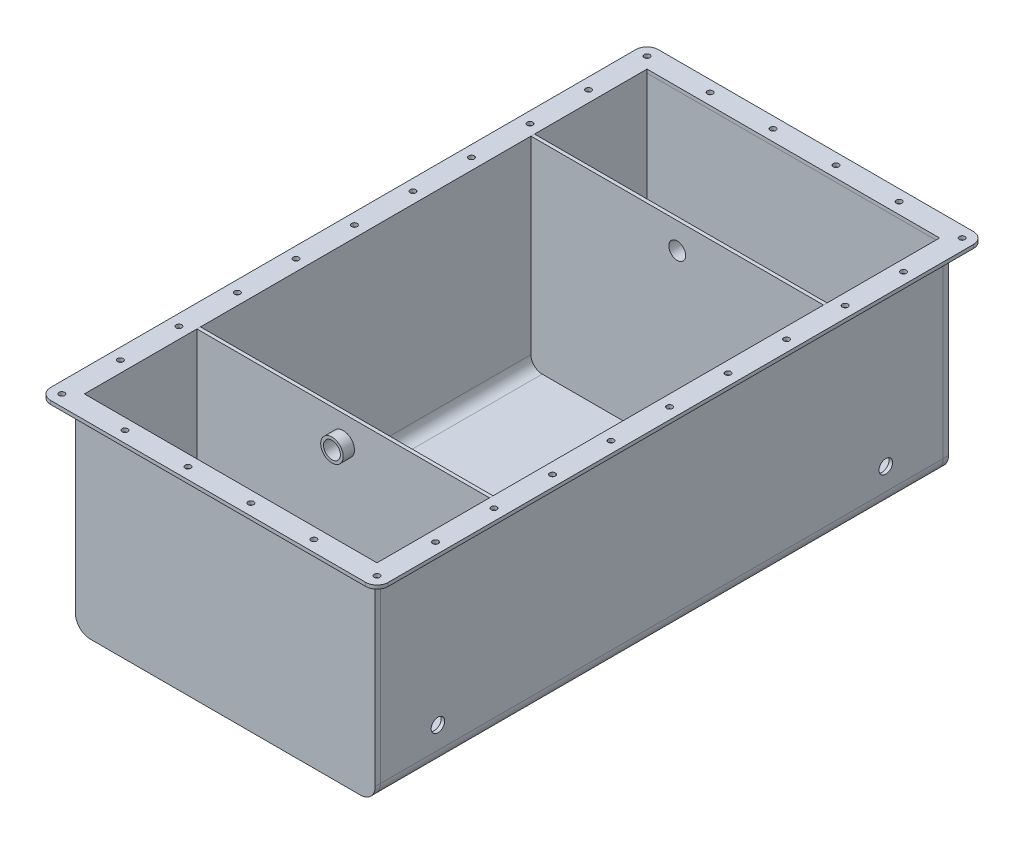
SolidWorks part; units mm, degrees
material "5052-H32"
ref_plane "Front Plane" through (0, 0, 0) normal (0, 0, 1) x (1, 0, 0)
ref_plane "Top Plane" through (0, 0, 0) normal (0, 1, 0) x (1, 0, 0)
ref_plane "Right Plane" through (0, 0, 0) normal (1, 0, 0) x (0, 0, -1)
sketch "Sketch2" plane through (0, 0, 0) normal (0, 0, 1) x (1, 0, 0)
  line L0 (-130, 0) -> (130, 0)
  line L1 (-130, 0) -> (-130, 175)
  line L2 (130, 0) -> (130, 175)
  line L3 (-133.175, -3.175) -> (-133.175, 175)
  line L4 (-133.175, -3.175) -> (133.175, -3.175)
  line L5 (133.175, -3.175) -> (133.175, 175)
  line L6 (-133.175, 175) -> (-130, 175)
  line L7 (130, 175) -> (133.175, 175)
  point P4 (0, 0)
  dimension "D1" = 260
  dimension "D3" = 175
  dimension "D4" = 175
  dimension "D2" = 3.175
  dimension "D5" = 3.175
  dimension "D6" = 3.175
extrude "Interior Dim" add sketch "Sketch2" against normal blind 500
fillet "Fillet2" radius 10 2 edges at (-130, 0, -250) (130, 0, -250)
fillet "Fillet3" radius 13.175 2 edges at (-133.175, -3.175, -250) (133.175, -3.175, -250)
ref_plane "Plane1" through (0, 0, 0) normal (0, 0, 1) x (1, 0, 0)
sketch "Sketch4" plane through (0, 0, 0) normal (0, 0, 1) x (1, 0, 0)
  line L0 (-130, 175) -> (130, 175)
  line L9 (-120, -3.175) -> (120, -3.175)
  line L10 (133.175, 10) -> (133.175, 175)
  line L11 (133.175, 175) -> (130, 175)
  line L12 (130, 175) -> (130, 10)
  line L13 (120, 0) -> (-120, 0)
  line L14 (-130, 10) -> (-130, 175)
  line L15 (-130, 175) -> (-133.175, 175)
  line L16 (-133.175, 175) -> (-133.175, 10)
  line L17 (-120, -3.175) -> (120, -3.175)
  line L18 (133.175, 10) -> (133.175, 175)
  line L19 (133.175, 175) -> (130, 175)
  line L23 (-130, 175) -> (-133.175, 175)
  line L24 (-133.175, 175) -> (-133.175, 10)
  arc A4 (120, -3.175) -> (133.175, 10) centre (120, 10) ccw
  arc A5 (120, 0) -> (130, 10) centre (120, 10) ccw
  arc A6 (-130, 10) -> (-120, 0) centre (-120, 10) ccw
  arc A7 (120, -3.175) -> (133.175, 10) centre (120, 10) ccw
  arc A9 (-133.175, 10) -> (-120, -3.175) centre (-120, 10) ccw
  arc A10 (-133.175, 10) -> (-120, -3.175) centre (-120, 10) ccw
  dimension "D1" = 0
extrude "Endcap1" add sketch "Sketch4" along normal blind 4.7625 separate body
ref_plane "Plane2" through (0, 0, -500) normal (0, 0, -1) x (-1, 0, 0)
sketch "Sketch5" plane through (0, 0, -500) normal (0, 0, -1) x (-1, 0, 0)
  line L8 (133.175, 175) -> (-133.175, 175)
  line L16 (-133.175, 175) -> (-133.175, 10)
  line L17 (-120, -3.175) -> (120, -3.175)
  line L18 (133.175, 10) -> (133.175, 175)
  line L19 (133.175, 175) -> (130, 175)
  line L20 (130, 175) -> (130, 10)
  line L21 (120, 0) -> (-120, 0)
  line L22 (-130, 10) -> (-130, 175)
  line L23 (-130, 175) -> (-133.175, 175)
  line L24 (-133.175, 175) -> (-133.175, 10)
  line L25 (-120, -3.175) -> (120, -3.175)
  line L26 (133.175, 10) -> (133.175, 175)
  arc A6 (-133.175, 10) -> (-120, -3.175) centre (-120, 10) ccw
  arc A7 (-133.175, 10) -> (-120, -3.175) centre (-120, 10) ccw
  arc A8 (120, 0) -> (130, 10) centre (120, 10) ccw
  arc A9 (-130, 10) -> (-120, 0) centre (-120, 10) ccw
  arc A12 (120, -3.175) -> (133.175, 10) centre (120, 10) ccw
  arc A13 (120, -3.175) -> (133.175, 10) centre (120, 10) ccw
  dimension "D1" = 0
ref_plane "Compartment1" through (0, 0, -100) normal (0, 0, -1) x (-1, 0, 0)
sketch "Sketch7" plane through (0, 0, -100) normal (0, 0, -1) x (-1, 0, 0)
  line L1 (130, 175) -> (-130, 175)
  line L10 (-120, -3.175) -> (120, -3.175)
  line L11 (-133.175, 175) -> (-133.175, 10)
  line L12 (-130, 175) -> (-133.175, 175)
  line L13 (-130, 10) -> (-130, 175)
  line L14 (120, 0) -> (-120, 0)
  line L15 (130, 175) -> (130, 10)
  line L16 (133.175, 175) -> (130, 175)
  line L17 (133.175, 10) -> (133.175, 175)
  line L21 (-130, 10) -> (-130, 175)
  line L22 (120, 0) -> (-120, 0)
  line L23 (130, 175) -> (130, 10)
  arc A5 (-130, 10) -> (-120, 0) centre (-120, 10) ccw
  arc A6 (120, 0) -> (130, 10) centre (120, 10) ccw
  arc A7 (-133.175, 10) -> (-120, -3.175) centre (-120, 10) ccw
  arc A8 (120, -3.175) -> (133.175, 10) centre (120, 10) ccw
  arc A9 (-130, 10) -> (-120, 0) centre (-120, 10) ccw
  arc A10 (120, 0) -> (130, 10) centre (120, 10) ccw
  dimension "D1" = 0
extrude "Compartment1_Boss" add sketch "Sketch7" along normal blind 3.175 separate body contours L22 A10 L23 L1 L21 A9 region at (0, 87.5805, -100)
ref_plane "Plane5" through (0, 175, 0) normal (0, 1, 0) x (1, 0, 0)
sketch "Sketch9" plane through (0, 175, 0) normal (0, 1, 0) x (1, 0, 0)
  line L0 (97.9962, 500) -> (-97.9962, 500) construction
  line L1 (-130, 500) -> (130, 500)
  line L2 (-130, 500) -> (-130, 0)
  line L3 (-130, 0) -> (130, 0)
  line L4 (130, 500) -> (130, 0)
  line L5 (-130, 0) -> (-130, 500) construction
  line L6 (-97.9962, 0) -> (97.9962, 0) construction
  line L7 (130, 500) -> (130, 0) construction
  line L8 (-150, 520) -> (-150, -20)
  line L9 (-150, -20) -> (150, -20)
  line L10 (150, 520) -> (150, -20)
  line L11 (-150, 520) -> (150, 520)
extrude "Lid_Flange" add sketch "Sketch9" along normal blind 3.175 separate body contours L11 L8 L9 L10 L1 L4 region at (0, 175, -513.8226)
fillet "Fillet4" radius 10 4 edges at (-150, 176.5875, -520) (150, 176.5875, -520) (150, 176.5875, 20) (-150, 176.5875, 20)
extrude "Endcap2" add sketch "Sketch5" along normal blind 4.7625 separate body
ref_plane "Compartment2" through (0, 0, -400) normal (0, 0, 1) x (1, 0, 0)
sketch "Sketch13" plane through (0, 0, -400) normal (0, 0, 1) x (1, 0, 0)
  line L0 (130, 175) -> (-130, 175)
  line L1 (133.175, 175) -> (130, 175) construction
  line L2 (130, 175) -> (130, 10) construction
  line L3 (-140, 175) -> (140, 175) construction
  line L4 (-130, 10) -> (-130, 175) construction
  line L5 (130, 175) -> (130, 10)
  line L6 (-130, 175) -> (-130, 10)
  line L7 (120, 0) -> (-120, 0)
  arc A0 (120, 0) -> (130, 10) centre (120, 10) ccw construction
  arc A1 (-130, 10) -> (-120, 0) centre (-120, 10) ccw construction
  arc A2 (-130, 10) -> (-120, 0) centre (-120, 10) ccw
  arc A3 (130, 10) -> (120, 0) centre (120, 10) cw
  dimension "D1" = 175
extrude "Compartment2_Boss" add sketch "Sketch13" along normal blind 3.175
sketch "Sketch16" plane through (-133.175, 0, 0) normal (-1, 0, 0) x (0, 0, 1)
  line L0 (-500, 0) -> (-400, 0) construction
  line L1 (-500, 175) -> (-500, 10) construction
  line L2 (0, 175) -> (0, 10) construction
  line L3 (-51, 29.5) -> (-449, 29.5) construction
  circle A0 centre (-449, 29.5) radius 6
  circle A1 centre (-51, 29.5) radius 6
  dimension "D1" = 12
  dimension "D4" = 12
  dimension "D2" = 29.5
  dimension "D3" = 51
  dimension "D5" = 51
extrude "Bearing_holes" cut sketch "Sketch16" against normal through all
sketch "Sketch17" plane through (0, 0, -400) normal (0, 0, -1) x (-1, 0, 0)
  line L0 (142.7388, 175) -> (-142.7388, 175) construction
  line L1 (130, 175) -> (130, 10) construction
  circle A0 centre (0, 155) radius 7.5
  circle A1 centre (0, 155) radius 10
  dimension "D1" = 15
  dimension "D4" = 20
  dimension "D2" = 20
  dimension "D3" = 130
extrude "Wire_Passthrough" cut sketch "Sketch17" against normal up to surface (300 mm away) contours A0 region at (0, 155, -400) up to face at (0, 60.9763, -100)
sketch "Sketch18" plane through (0, 175, 0) normal (0, 1, 0) x (1, 0, 0)
  line L1 (-130, 400) -> (130, 400)
  line L2 (-130, 400) -> (-130, 396.825)
  line L3 (-130, 396.825) -> (130, 396.825)
  line L4 (130, 400) -> (130, 396.825)
  line L5 (-130, 103.175) -> (130, 103.175)
  line L6 (-130, 103.175) -> (-130, 100)
  line L7 (-130, 100) -> (130, 100)
  line L8 (130, 103.175) -> (130, 100)
extrude "Boss-Extrude1" add sketch "Sketch18" along normal blind 3.18
extrude "Wire_Tube_2" add sketch "Sketch17<3>" along normal blind 10
sketch "Sketch17<3>" plane through (0, 0, -400) normal (0, 0, -1) x (-1, 0, 0) same geometry as "Sketch17"
sketch "Sketch19" plane through (0, 0, -100) normal (0, 0, 1) x (1, 0, 0)
  circle A0 centre (0, 155) radius 10
  circle M1 centre (0, 155) radius 7.5
  dimension "D1" = 20
extrude "Wire_Tube_1" add sketch "Sketch19" along normal blind 10 contours A0 M1 region at (-9.7172, 155, -100)
sketch "Sketch20" plane through (0, 175, 175) normal (0, 1, 0) x (1, 0, 0)
  line L0 (130, 425) -> (-130, 425) construction
  line L1 (-130, 675) -> (130, 675) construction
  line L2 (-130, 675) -> (-130, 175) construction
  line L3 (-130, 175) -> (130, 175) construction
  line L4 (130, 675) -> (130, 175) construction
  line L5 (130, 571.825) -> (130, 278.175) construction
  line L7 (0, 425) -> (0, 175) construction
  line L8 (-150, 695) -> (-150, 155) construction
  line L9 (-150, 155) -> (150, 155) construction
  line L10 (150, 695) -> (150, 155) construction
  line L11 (-150, 695) -> (150, 695) construction
  line L12 (-130, 571.825) -> (-130, 278.175) construction
  circle A0 centre (-140, 165) radius 2.5
  circle A2 centre (-140, 217) radius 2.5
  circle A3 centre (-140, 269) radius 2.5
  circle A4 centre (-140, 321) radius 2.5
  circle A5 centre (-140, 373) radius 2.5
  circle A6 centre (-140, 425) radius 2.5
  circle A7 centre (-140, 477) radius 2.5
  circle A8 centre (-140, 529) radius 2.5
  circle A9 centre (-140, 581) radius 2.5
  circle A10 centre (-140, 633) radius 2.5
  circle A16 centre (-140, 685) radius 2.5
  circle A17 centre (-84, 685) radius 2.5
  circle A18 centre (-28, 685) radius 2.5
  circle A19 centre (28, 685) radius 2.5
  circle A20 centre (84, 685) radius 2.5
  circle A21 centre (140, 685) radius 2.5
  circle A22 centre (140, 633) radius 2.5
  circle A23 centre (140, 581) radius 2.5
  circle A24 centre (140, 529) radius 2.5
  circle A25 centre (140, 477) radius 2.5
  circle A26 centre (140, 425) radius 2.5
  circle A27 centre (140, 373) radius 2.5
  circle A28 centre (140, 321) radius 2.5
  circle A29 centre (140, 269) radius 2.5
  circle A30 centre (140, 217) radius 2.5
  circle A31 centre (140, 165) radius 2.5
  circle A37 centre (84, 165) radius 2.5
  circle A38 centre (28, 165) radius 2.5
  circle A39 centre (-28, 165) radius 2.5
  circle A40 centre (-84, 165) radius 2.5
  point P8 (-130, 425)
  point P16 (-120, 425)
  point P69 (0, 0)
  dimension "D4" = 5
  dimension "D3" = 10
  dimension "D9" = 250
  dimension "D2" = 500
  dimension "D10" = 10
  dimension "D11" = 260
  dimension "D1" = 20
  dimension "D8" = 11
  dimension "D5" = 6
  dimension "D6" = 11
  dimension "D7" = 5
extrude "Bolt_Holes" cut sketch "Sketch20" along normal up to next
equation "\"L\"= 500"
equation "\"W\"= 260"
equation "\"D1@Sketch2\"=\"W\""
equation "\"D1@Interior Dim\" = \"L\""
equation "\"H\"= 175"
equation "\"D3@Sketch2\"=\"H\""
equation "\"D4@Sketch2\"=\"H\""
equation "\"Compartment Width\"= 100"
equation "\"D1@Compartment2\"=\"Compartment Width\""
equation "\"D1@Compartment1\"=\"Compartment Width\""
equation "\"D1@Sketch13\"=\"H\""
equation "\"D3@Sketch17\"=\"W\"/2"
equation "\"T\"= 4.7625 * 2 / 3"
equation "\"D1@Lid_Flange\"=\"T\""
equation "\"D1@Fillet3\"=\"T\"+10"
equation "\"D1@Compartment1_Boss\"=\"T\""
equation "\"D1@Compartment2_Boss\"=\"T\""
equation "\"D2@Sketch20\"=\"L\""
equation "\"D11@Sketch20\"=\"W\""
equation "\"D9@Sketch20\"=\"L\"/2"
